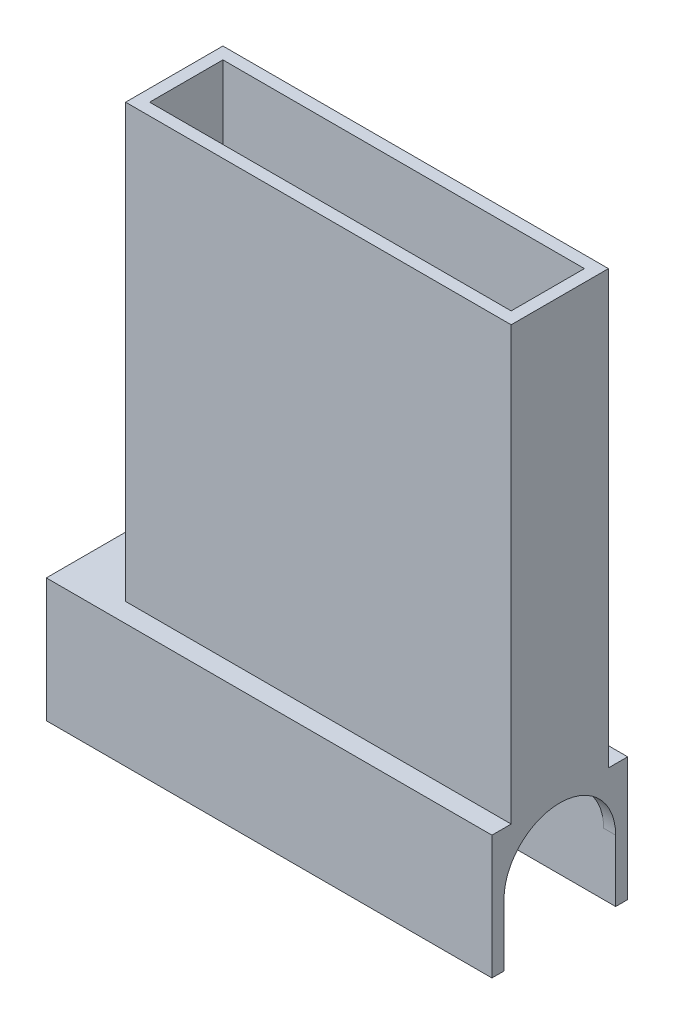
SolidWorks part; units mm, degrees
ref_plane "Front Plane" through (0, 0, 0) normal (0, 0, 1) x (1, 0, 0)
ref_plane "Top Plane" through (0, 0, 0) normal (0, 1, 0) x (1, 0, 0)
ref_plane "Right Plane" through (0, 0, 0) normal (1, 0, 0) x (0, 0, -1)
sketch "Sketch1" plane through (0, 0, 0) normal (0, 1, 0) x (1, 0, 0)
  line L0 (-16.05, 4.05) -> (16.05, 4.05)
  line L5 (-15.05, -3.05) -> (15.05, 3.05) construction
  line L6 (-15.05, 3.05) -> (15.05, -3.05) construction
  line L7 (16.05, -4.05) -> (16.05, 4.05)
  line L8 (-16.05, -4.05) -> (16.05, -4.05)
  line L9 (-16.05, -4.05) -> (-16.05, 4.05)
  point P0 (0, 0)
  dimension "D3" = 8.1
  dimension "D4" = 32.1
extrude "Boss-Extrude3" add sketch "Sketch1" along normal blind 36
sketch "Sketch3" plane through (0, 0, 0) normal (0, -1, 0) x (1, 0, 0)
  line L0 (-16.05, 4.05) -> (16.05, 4.05) construction
  line L8 (16.05, -5.65) -> (-21.05, -5.65)
  line L9 (16.05, -5.65) -> (16.05, 5.65)
  line L10 (16.05, 5.65) -> (-21.05, 5.65)
  line L11 (-21.05, -5.65) -> (-21.05, 5.65)
  point P0 (0, 0)
  point P8 (-2.5, -5.65)
  dimension "D1" = 11.3
  dimension "D2" = 37.1
  dimension "D3" = 1.6
  dimension "D4" = 2.5
extrude "Boss-Extrude4" add sketch "Sketch3" along normal blind 10.3
sketch "Sketch4" plane through (0, -10.3, 0) normal (0, -1, 0) x (1, 0, 0)
  line L8 (15.05, -4.65) -> (15.05, 4.65)
  line L9 (15.05, 4.65) -> (-20.05, 4.65)
  line L10 (15.05, 4.65) -> (-20.05, 4.65)
  line L11 (-20.05, 4.65) -> (-20.05, -4.65)
  line L12 (15.05, -4.65) -> (15.05, 4.65)
  line L16 (-20.05, 4.65) -> (-20.05, -4.65)
  line L17 (-20.05, -4.65) -> (15.05, -4.65)
  line L18 (-20.05, -4.65) -> (15.05, -4.65)
  dimension "D1" = 1
extrude "Cut-Extrude2" cut sketch "Sketch4" against normal blind 9.3
sketch "Sketch5" plane through (0, 36, 0) normal (0, 1, 0) x (1, 0, 0)
  line L8 (-15.05, 3.05) -> (-15.05, -3.05)
  line L9 (-15.05, -3.05) -> (15.05, -3.05)
  line L10 (15.05, -3.05) -> (15.05, 3.05)
  line L11 (15.05, 3.05) -> (-15.05, 3.05)
  line L12 (-15.05, 3.05) -> (-15.05, -3.05)
  line L13 (-15.05, -3.05) -> (15.05, -3.05)
  line L14 (15.05, -3.05) -> (15.05, 3.05)
  line L15 (15.05, 3.05) -> (-15.05, 3.05)
  dimension "D1" = 1
extrude "Cut-Extrude3" cut sketch "Sketch5" against normal through all
sketch "Sketch7" plane through (16.05, 0, 0) normal (1, 0, 0) x (0, 0, -1)
  line L0 (0, -10.3) -> (0, 0) construction
  line L1 (5.65, -10.3) -> (-5.65, -10.3) construction
  line L2 (-5.65, -5.15) -> (5.65, -5.15) construction
  line L3 (-5.65, -10.3) -> (-5.65, 0) construction
  line L4 (5.65, -10.3) -> (5.65, 0) construction
  line L6 (4.65, -5.15) -> (4.65, -10.3)
  line L8 (-4.65, -5.15) -> (-4.65, -10.3)
  line L9 (4.65, -10.3) -> (-4.65, -10.3)
  arc A0 (4.65, -5.15) -> (-4.65, -5.15) centre (0, -5.15) ccw
  dimension "D1" = 9.3
extrude "Cut-Extrude4" cut sketch "Sketch7" against normal through all
